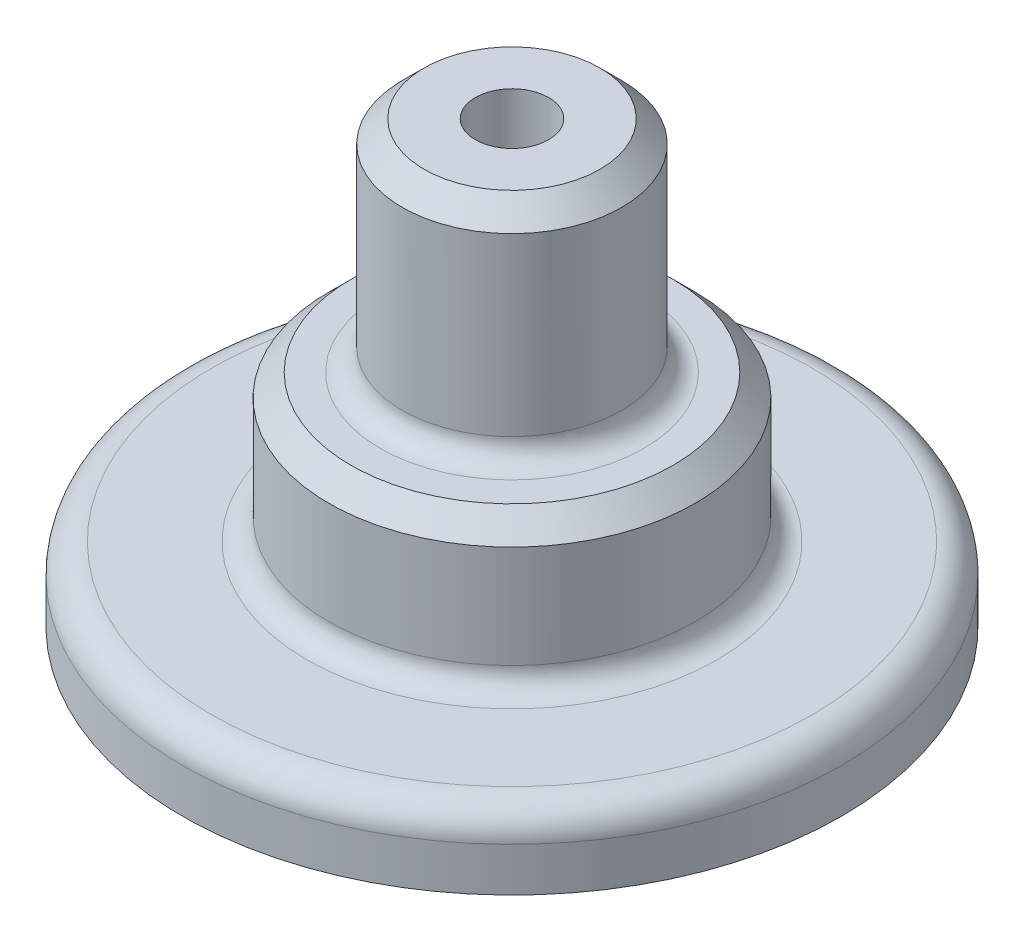
SolidWorks part; units mm, degrees
ref_plane "Front Plane" through (0, 0, 0) normal (0, 0, 1) x (1, 0, 0)
ref_plane "Top Plane" through (0, 0, 0) normal (0, 1, 0) x (1, 0, 0)
ref_plane "Right Plane" through (0, 0, 0) normal (1, 0, 0) x (0, 0, -1)
sketch "Sketch2" plane through (0, 0, 0) normal (0, 0, 1) x (1, 0, 0)
  line L0 (10, 120) -> (10, 0)
  line L1 (10, 0) -> (100, 0)
  line L2 (100, 0) -> (100, 20)
  line L3 (100, 20) -> (60, 20)
  line L4 (60, 20) -> (60, 60)
  line L5 (60, 60) -> (40, 60)
  line L6 (40, 60) -> (40, 120)
  line L7 (40, 120) -> (10, 120)
  dimension "D1" = 30
  dimension "D2" = 50
  dimension "D3" = 90
  dimension "D4" = 20
  dimension "D5" = 60
  dimension "D6" = 120
  dimension "D7" = 10
revolve "Revolve1" add sketch "Sketch2" angle 360 about L0
fillet "Fillet2" radius 8 1 edges at (-80, 20, 0)
fillet "Fillet3" radius 6 1 edges at (-40, 20, 0)
fillet "Fillet4" radius 6 1 edges at (-20, 60, 0)
sketch "Sketch3" plane through (0, 120, 0) normal (0, 1, 0) x (1, 0, 0)
  circle A0 centre (10, 0) radius 10
  dimension "D1" = 20
  dimension "D2" = 10
extrude "Cut-Extrude2" cut sketch "Sketch3" against normal through all and the other way blind 10
chamfer "Chamfer2" distance 6 2 edges at (-40, 60, 0) (-20, 120, 0)
